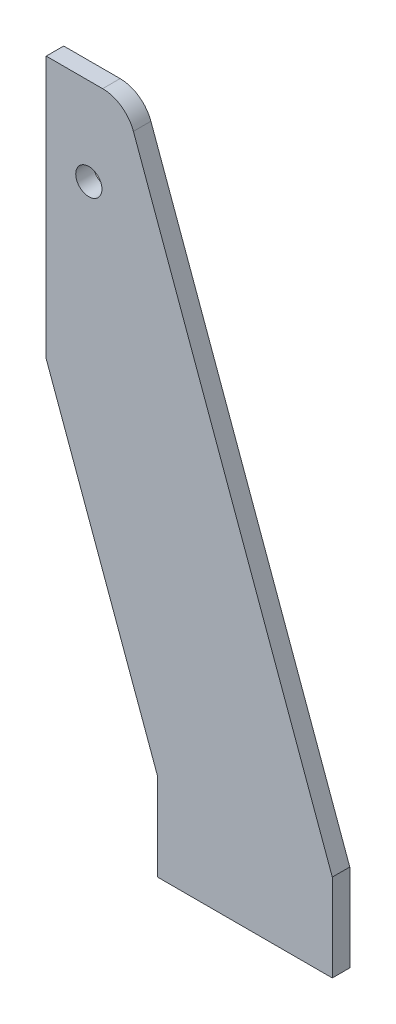
SolidWorks part; units mm, degrees
ref_plane "Alzado" through (0, 0, 0) normal (0, 0, 1) x (1, 0, 0)
ref_plane "Planta" through (0, 0, 0) normal (0, 1, 0) x (1, 0, 0)
ref_plane "Vista lateral" through (0, 0, 0) normal (1, 0, 0) x (0, 0, -1)
sketch "Croquis1" plane through (0, 0, 0) normal (0, 0, 1) x (1, 0, 0)
  line L0 (80, 0) -> (80, 40)
  line L1 (-50.9558, 300) -> (-25.1354, 300)
  line L2 (-50.9558, 300) -> (-50.9558, 180)
  line L3 (0, 0) -> (80, 0)
  line L4 (-11.04, 290.1303) -> (80, 40)
  line L9 (-50.9558, 180) -> (0, 40)
  line L11 (0, 40) -> (0, 0)
  arc A2 (-11.04, 290.1303) -> (-25.1354, 300) centre (-25.1354, 285) ccw
  point P6 (-50.9558, 300)
  dimension "D7" = 110
  dimension "D9" = 15
  dimension "D1" = 40
  dimension "D2" = 300
  dimension "D3" = 80
  dimension "D6" = 40
  dimension "D10" = 110
extrude "Saliente-Extruir1" add sketch "Croquis1" along normal blind 8
sketch "Croquis2" plane through (0, 0, 0) normal (0, 0, -1) x (-1, 0, 0)
  line L0 (25.1354, 300) -> (50.9558, 300) construction
  line L2 (50.9558, 300) -> (50.9558, 180) construction
  circle A0 centre (31.4558, 260) radius 6
  point P8 (50.9558, 230.2364)
  dimension "D3" = 12
  dimension "D1" = 40
  dimension "D2" = 19.5
extrude "Cortar-Extruir1" cut sketch "Croquis2" against normal through all
hole_wizard "Perforador para roscar para macho de roscar para M44" positions "Croquis7" profile "Croquis8" hole size "M4" standard "DIN"
sketch "Croquis7" plane through (0, 0, 0) normal (0, 0, -1) x (-1, 0, 0)
  line L0 (31.4558, 278.25) -> (31.4558, 241.75)
  circle A0 centre (31.4558, 260) radius 6 construction
  point P10 (31.4558, 278.25)
  point P12 (31.4558, 241.75)
  dimension "D1" = 18.25
  dimension "D2" = 18.25
sketch "Croquis8" plane through (-31.4558, 241.75, 0) normal (1, 0, 0) x (0, 1, 0)
  line L0 (0, 0) -> (0, 7.9914)
  line L1 (0, 7.9914) -> (1.65, 7)
  line L2 (1.65, 7) -> (1.65, 0)
  line L5 (1.65, 0) -> (0, 0)
  line L10 (0, 7.9914) -> (-1.65, 7) construction
  line L11 (0, -6.35) -> (0, 107.95) construction
  dimension "Diámetro de taladro" = 3.3
  dimension "Profundidad de taladro" = 7
  dimension "Ángulo de perforador" = 118
